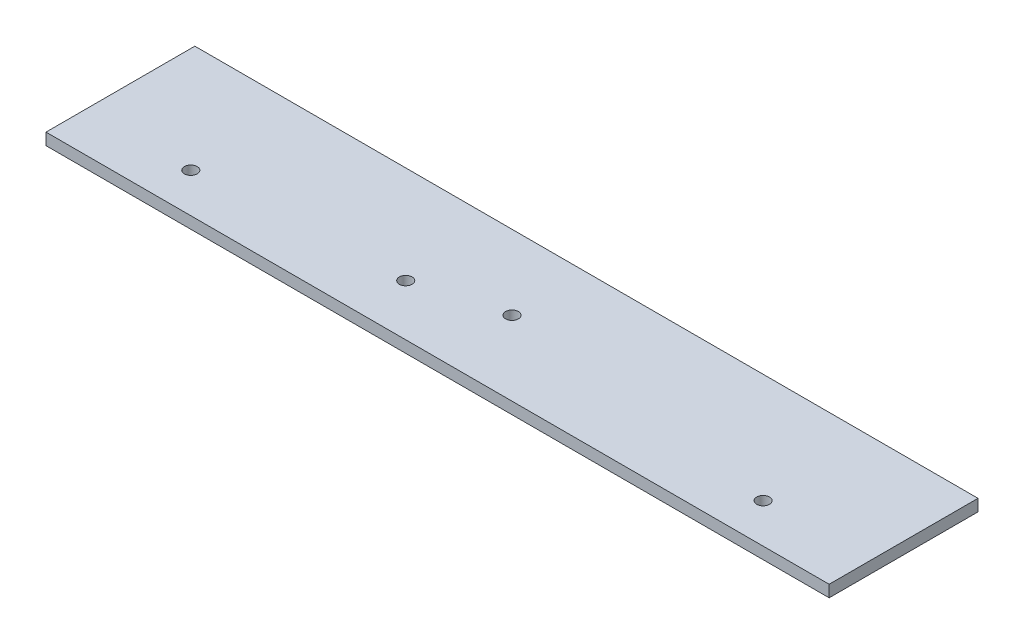
SolidWorks part; units mm, degrees
ref_plane "Front Plane" through (0, 0, 0) normal (0, 0, 1) x (1, 0, 0)
ref_plane "Top Plane" through (0, 0, 0) normal (0, 1, 0) x (1, 0, 0)
ref_plane "Right Plane" through (0, 0, 0) normal (1, 0, 0) x (0, 0, -1)
sketch "Sketch1" plane through (0, 0, 0) normal (0, 1, 0) x (1, 0, 0)
  line L0 (-71, -8.695) -> (71, -8.695) construction
  line L2 (-97.1504, -18.4656) -> (97.1504, -18.4656)
  line L3 (-97.1504, -18.4656) -> (-97.1504, 18.4656)
  line L4 (-97.1504, 18.4656) -> (97.1504, 18.4656)
  line L5 (97.1504, -18.4656) -> (97.1504, 18.4656)
  line L6 (-97.1504, -18.4656) -> (97.1504, 18.4656) construction
  line L7 (-97.1504, 18.4656) -> (97.1504, -18.4656) construction
  circle A0 centre (-71, -8.695) radius 1.5875
  circle A1 centre (71, -8.695) radius 1.5875
  circle A2 centre (0, 0) radius 1.5875
  circle A3 centre (-20.62, -5.75) radius 1.5875
  point P6 (0, 0)
  dimension "D2" = 3.175
  dimension "D1" = 142
  dimension "D3" = 20.62
  dimension "D4" = 5.75
  dimension "D5" = 8.695
extrude "Boss-Extrude1" add sketch "Sketch1" along normal mid plane 2.921
sketch "Sketch2" plane through (0, -1.4605, 0) normal (0, -1, 0) x (-1, 0, 0)
  line L0 (20.62, -5.75) -> (26.2458, -5.75) construction
